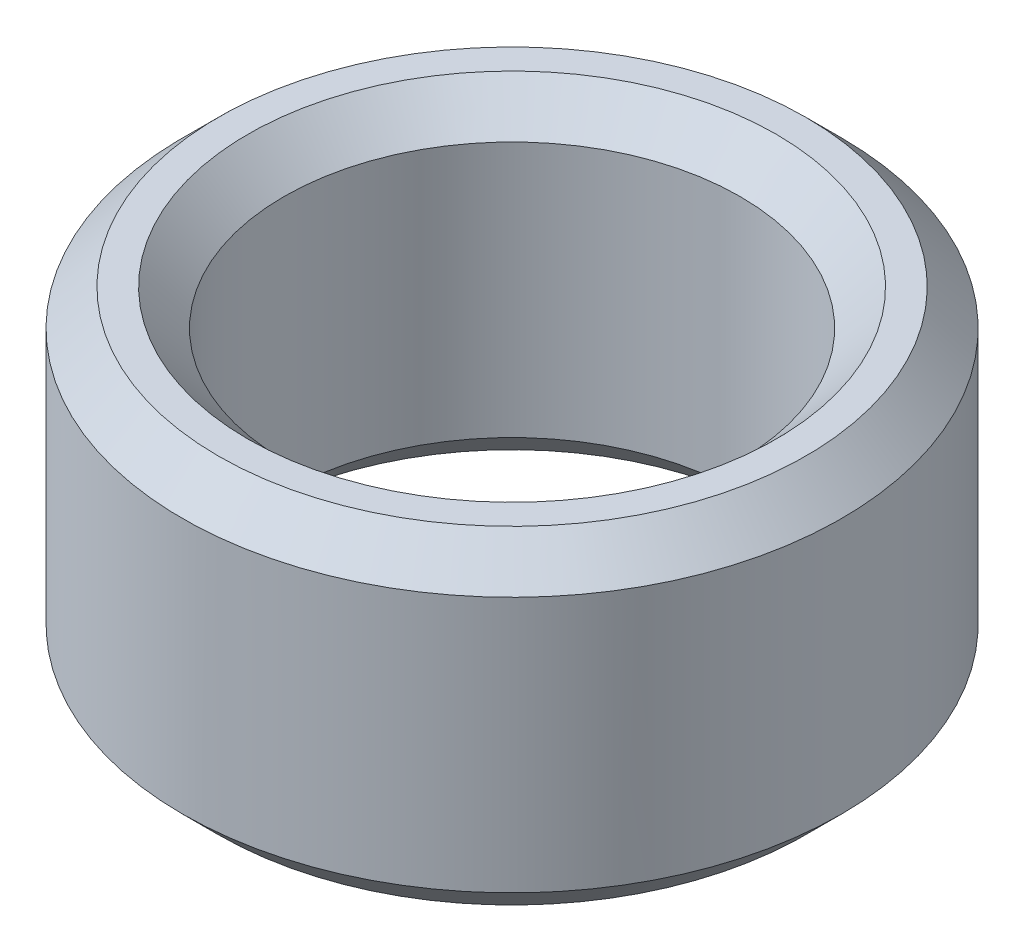
SolidWorks part; units mm, degrees
ref_plane "Front Plane" through (0, 0, 0) normal (0, 0, 1) x (1, 0, 0)
ref_plane "Top Plane" through (0, 0, 0) normal (0, 1, 0) x (1, 0, 0)
ref_plane "Right Plane" through (0, 0, 0) normal (1, 0, 0) x (0, 0, -1)
sketch "Sketch1" plane through (0, 0, 0) normal (0, 1, 0) x (1, 0, 0)
  circle A0 centre (0, 0) radius 27.5
  dimension "SLEEVE_OD" = 55
extrude "Boss-Extrude1" add sketch "Sketch1" along normal blind 27.3647
sketch "Sketch2" plane through (0, 0, 0) normal (0, 1, 0) x (1, 0, 0)
  circle A0 centre (0, 0) radius 19.0338
  dimension "BORE_D" = 38.0676
extrude "Cut-Extrude1" cut sketch "Sketch2" along normal through all
chamfer "Chamfer1" distance 3.0034 angle 45 4 edges at (0, 27.3647, 19.0338) (0, 0, 19.0338) (0, 0, 27.5) (0, 27.3647, 27.5)
